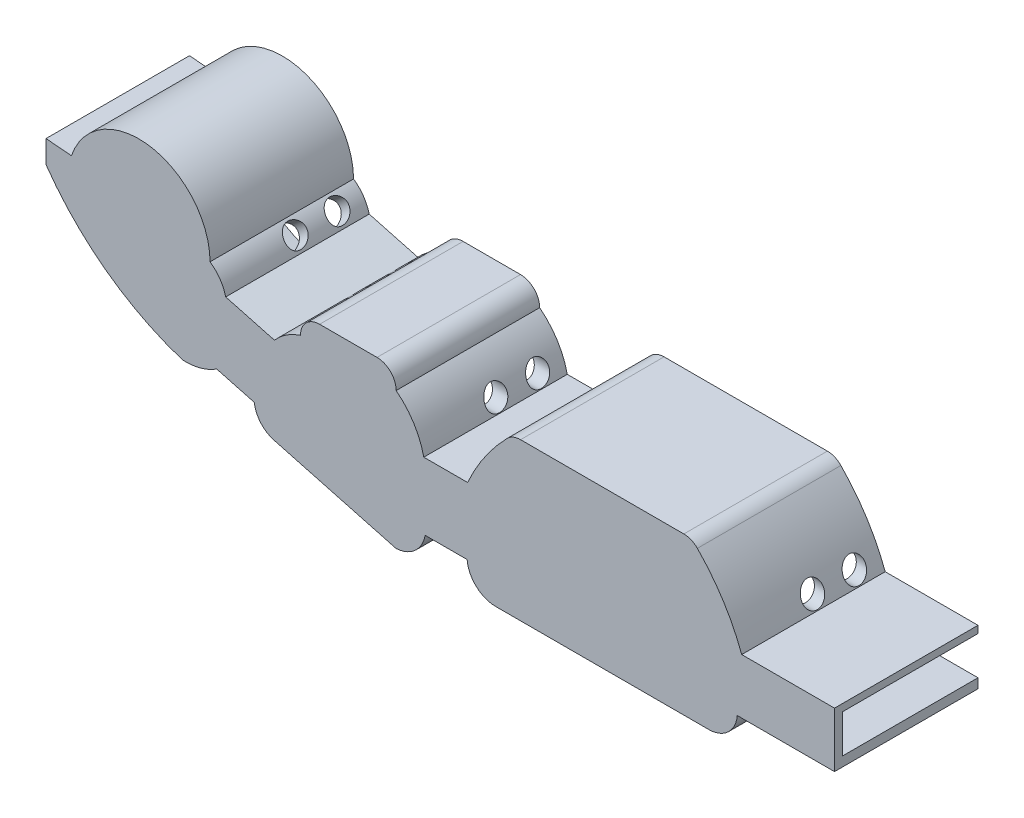
SolidWorks part; units mm, degrees
ref_plane "Front Plane" through (0, 0, 0) normal (0, 0, 1) x (1, 0, 0)
ref_plane "Top Plane" through (0, 0, 0) normal (0, 1, 0) x (1, 0, 0)
ref_plane "Right Plane" through (0, 0, 0) normal (1, 0, 0) x (0, 0, -1)
sketch "Sketch1" plane through (0, 0, 0) normal (0, 0, 1) x (1, 0, 0)
  line L5 (-89.4257, 12.3858) -> (-89.4257, 15.2174)
  line L6 (-89.4257, 15.2174) -> (-86.2372, 14.9459)
  line L11 (-29.6547, 9.152) -> (-29.9579, 10.6577)
  line L13 (-85.3867, 9.2655) -> (-88.6842, 13.2092)
  line L14 (-88.6842, 13.2092) -> (-88.6842, 13.9453)
  line L17 (-88.6842, 13.9453) -> (-88.2985, 13.5047)
  line L19 (-43.5928, 3.095) -> (-35.5928, 3.095)
  line L20 (-35.5971, -2.905) -> (-43.6235, -2.905)
  line L21 (-55.2174, 10.6822) -> (-55.1336, 10.6822)
  line L22 (-59.126, -2.5288) -> (-46.5703, -5.8983)
  line L23 (-11.1807, 10.652) -> (-11.4807, 9.152)
  line L24 (-11.4807, 9.152) -> (-11.7807, 10.652)
  line L25 (-11.7807, 10.652) -> (-12.4807, 10.652)
  line L30 (-86.6408, 12.3858) -> (-88.2985, 13.5047)
  line L36 (-12.4807, 10.652) -> (-12.7807, 9.152)
  line L40 (-12.7807, 9.152) -> (-13.0807, 10.652)
  line L41 (-13.0807, 10.652) -> (-13.7547, 10.652)
  line L43 (-47.904, 12.2025) -> (-55.104, 12.2025)
  line L44 (-60.579, -3.3191) -> (-45.5122, -7.3625)
  line L47 (-13.7547, 10.652) -> (-14.0547, 9.152)
  line L48 (-14.0547, 9.152) -> (-14.3547, 10.652)
  line L49 (-14.3547, 10.652) -> (-15.0547, 10.652)
  line L50 (-15.0547, 10.652) -> (-15.3547, 9.152)
  line L51 (-15.3547, 9.152) -> (-15.6547, 10.652)
  line L52 (-15.6547, 10.652) -> (-16.3547, 10.652)
  line L53 (-16.3547, 10.652) -> (-16.6547, 9.152)
  line L54 (-16.6547, 9.152) -> (-16.9547, 10.652)
  line L55 (-16.9547, 10.652) -> (-17.6547, 10.652)
  line L56 (-17.6547, 10.652) -> (-17.9547, 9.152)
  line L57 (-17.9547, 9.152) -> (-18.2547, 10.652)
  line L58 (-18.2547, 10.652) -> (-18.9547, 10.652)
  line L59 (-18.9547, 10.652) -> (-19.2547, 9.152)
  line L60 (-19.2547, 9.152) -> (-19.5547, 10.652)
  line L61 (-19.5547, 10.652) -> (-20.2547, 10.652)
  line L62 (-20.2547, 10.652) -> (-20.5547, 9.152)
  line L63 (-20.5547, 9.152) -> (-20.8547, 10.652)
  line L64 (-20.8547, 10.652) -> (-21.5547, 10.652)
  line L65 (-21.5547, 10.652) -> (-21.8547, 9.152)
  line L66 (-21.8547, 9.152) -> (-22.1547, 10.652)
  line L67 (-22.1547, 10.652) -> (-22.8547, 10.652)
  line L68 (-22.8547, 10.652) -> (-23.1547, 9.152)
  line L69 (-23.1547, 9.152) -> (-23.4547, 10.652)
  line L70 (-23.4547, 10.652) -> (-24.1547, 10.652)
  line L71 (-24.1547, 10.652) -> (-24.4547, 9.152)
  line L72 (-24.4547, 9.152) -> (-24.7547, 10.652)
  line L73 (-24.7547, 10.652) -> (-25.4547, 10.652)
  line L74 (-25.4547, 10.652) -> (-25.7547, 9.152)
  line L75 (-25.7547, 9.152) -> (-26.0547, 10.652)
  line L76 (-26.0547, 10.652) -> (-26.7547, 10.652)
  line L77 (-26.7547, 10.652) -> (-27.0547, 9.152)
  line L78 (-27.0547, 9.152) -> (-27.3547, 10.652)
  line L79 (-27.3547, 10.652) -> (-28.0547, 10.652)
  line L80 (-28.0547, 10.652) -> (-28.3547, 9.152)
  line L81 (-28.3547, 9.152) -> (-28.6547, 10.652)
  line L82 (-28.6547, 10.652) -> (-29.3547, 10.652)
  line L83 (-29.3547, 10.652) -> (-29.6547, 9.152)
  line L100 (-49.2174, 10.6822) -> (-49.3596, 10.6822)
  line L101 (-49.3596, 10.6822) -> (-49.6596, 9.1822)
  line L102 (-49.6596, 9.1822) -> (-49.9596, 10.6822)
  line L103 (-49.9596, 10.6822) -> (-50.6596, 10.6822)
  line L104 (-50.6596, 10.6822) -> (-50.9596, 9.1822)
  line L105 (-50.9596, 9.1822) -> (-51.2596, 10.6822)
  line L106 (-51.2596, 10.6822) -> (-51.9336, 10.6822)
  line L107 (-51.9336, 10.6822) -> (-52.2336, 9.1822)
  line L108 (-52.2336, 9.1822) -> (-52.5336, 10.6822)
  line L109 (-52.5336, 10.6822) -> (-53.2336, 10.6822)
  line L110 (-53.2336, 10.6822) -> (-53.5336, 9.1822)
  line L111 (-53.5336, 9.1822) -> (-53.8336, 10.6822)
  line L112 (-53.8336, 10.6822) -> (-54.5336, 10.6822)
  line L113 (-54.5336, 10.6822) -> (-54.8336, 9.1822)
  line L114 (-54.8336, 9.1822) -> (-55.1336, 10.6822)
  line L118 (-70.5436, 14.8576) -> (-70.8436, 12.8576)
  line L119 (-70.8436, 12.8576) -> (-71.1436, 15.955)
  line L120 (-71.8436, 16.8755) -> (-72.1436, 15.6755)
  line L121 (-72.1436, 15.6755) -> (-72.4436, 17.4876)
  line L122 (-73.1436, 18.0603) -> (-73.4436, 16.9603)
  line L123 (-73.4436, 16.9603) -> (-73.7436, 18.4574)
  line L124 (-74.4436, 18.8313) -> (-74.7436, 17.8313)
  line L125 (-74.7436, 17.8313) -> (-75.0436, 19.0854)
  line L126 (-75.7436, 19.313) -> (-76.0436, 18.263)
  line L127 (-76.0436, 18.263) -> (-76.3436, 19.4536)
  line L128 (-77.0436, 19.5578) -> (-77.3436, 18.4578)
  line L129 (-77.3436, 18.4578) -> (-77.6436, 19.5977)
  line L130 (-78.3448, 19.5875) -> (-78.6448, 18.3969)
  line L131 (-78.6448, 18.3969) -> (-78.9448, 19.5298)
  line L132 (-79.6426, 19.4048) -> (-79.9426, 18.1477)
  line L133 (-79.9426, 18.1477) -> (-80.2426, 19.2451)
  line L134 (-80.9421, 18.9938) -> (-81.2421, 17.6938)
  line L135 (-81.2421, 17.6938) -> (-81.5421, 18.7169)
  line L136 (-82.2402, 18.3139) -> (-82.5402, 16.8139)
  line L137 (-82.5402, 16.8139) -> (-82.8402, 17.886)
  line L138 (-83.5418, 17.2662) -> (-83.8418, 15.3662)
  line L139 (-83.8418, 15.3662) -> (-84.1418, 16.5999)
  line L148 (-60.7727, 7.6397) -> (-66.8852, 9.2801)
  line L156 (-65.7127, 0.2682) -> (-68.01, 0.8847)
  line L157 (-65.7127, 0.2682) -> (-63.3052, -0.3779)
  line L161 (-68.1187, 8.3687) -> (-60.3921, 6.2951)
  line L162 (-69.2607, 2.4628) -> (-61.42, 0.3587)
  line L163 (-41.8722, -4.105) -> (-36.6012, -4.105)
  line L164 (-42.0381, 4.295) -> (-36.5408, 4.295)
  line L167 (-19.6577, -6.2141) -> (-19.6577, -1.2141) construction
  line L168 (-32.5691, -6.2141) -> (-6.7463, -6.2141)
  line L169 (-29.8968, 12.2681) -> (-9.4143, 12.2681)
  line L170 (-19.6556, 4.8532) -> (-19.6556, 21.169) construction
  line L171 (8.2817, 1.895) -> (-3.6348, 1.895)
  line L172 (-10.5067, 10.652) -> (-11.1807, 10.652)
  line L173 (-9.9067, 10.652) -> (-9.3532, 10.652)
  line L174 (-6.3025, -7.4141) -> (-33.013, -7.4141)
  line L176 (-9.9067, 10.652) -> (-10.2067, 9.152)
  line L177 (-10.2067, 9.152) -> (-10.5067, 10.652)
  line L178 (-9.3532, 4.8532) -> (-9.3532, 10.652) construction
  line L179 (-3.7183, -2.905) -> (8.2817, -2.905)
  line L180 (-2.7142, -4.105) -> (9.4817, -4.105)
  line L183 (9.4817, 2.795) -> (9.4817, -4.105)
  line L184 (8.2817, 1.895) -> (8.2817, -2.905)
  line L185 (-2.1578, 2.795) -> (9.4817, 2.795)
  arc A2 (-85.3867, 9.2655) -> (-72.763, 0.8179) centre (-64.6402, 26.6123) ccw
  arc A5 (-29.9579, 10.6577) -> (-31.4838, 9.9746) centre (-29.9814, 8.6645) ccw
  arc A6 (-31.9681, 8.6822) -> (-35.5928, 3.095) centre (-27.6976, 1.9424) ccw
  arc A8 (-31.4838, 9.9746) -> (-31.9681, 8.6822) centre (-30.0017, 8.6822) ccw
  arc A14 (-69.8436, 11.2299) -> (-70.5436, 14.8576) centre (-77.8767, 11.5612) ccw
  arc A15 (-71.1436, 15.955) -> (-71.8436, 16.8755) centre (-77.8767, 11.5612) ccw
  arc A16 (-72.4436, 17.4876) -> (-73.1436, 18.0603) centre (-77.8767, 11.5612) ccw
  arc A19 (-35.5971, -2.905) -> (-32.5691, -6.2141) centre (-32.6131, -3.2144) ccw
  arc A25 (-73.7436, 18.4574) -> (-74.4436, 18.8313) centre (-77.8767, 11.5612) ccw
  arc A26 (-46.5703, -5.8983) -> (-43.6235, -2.905) centre (-46.8823, -2.644) ccw
  arc A27 (-61.42, 0.3587) -> (-59.126, -2.5288) centre (-58.5468, 0.2864) ccw
  arc A28 (-68.01, 0.8847) -> (-72.3211, -0.2669) centre (-71.9411, 6.9561) cw
  arc A29 (-75.0436, 19.0854) -> (-75.7436, 19.313) centre (-77.8767, 11.5612) ccw
  arc A30 (-76.3436, 19.4536) -> (-77.0436, 19.5578) centre (-77.8767, 11.5612) ccw
  arc A31 (-36.5408, 4.295) -> (-31.5909, 11.551) centre (-13.9301, -5.8132) cw
  arc A33 (-77.6436, 19.5977) -> (-78.3448, 19.5875) centre (-77.8767, 11.5612) ccw
  arc A34 (-72.763, 0.8179) -> (-69.2607, 2.4628) centre (-71.9865, 3.7157) ccw
  arc A37 (-68.1187, 8.3687) -> (-69.8436, 11.2299) centre (-72.1325, 7.8995) ccw
  arc A38 (-57.2174, 8.6822) -> (-60.3921, 6.2951) centre (-55.3158, 2.8486) ccw
  arc A41 (-43.5928, 3.095) -> (-47.2174, 8.6822) centre (-51.488, 1.9424) ccw
  arc A42 (-47.2174, 8.6822) -> (-49.2174, 10.6822) centre (-49.2174, 8.6822) ccw
  arc A43 (-55.2174, 10.6822) -> (-57.2174, 8.6822) centre (-55.2174, 8.6822) ccw
  arc A45 (-85.8314, 12.7286) -> (-86.6408, 12.3858) centre (-79.3152, -3.7856) ccw
  arc A47 (-29.8968, 12.2681) -> (-31.5909, 11.551) centre (-29.8968, 9.9085) ccw
  arc A48 (-78.9448, 19.5298) -> (-79.6426, 19.4048) centre (-77.8767, 11.5612) ccw
  arc A49 (-36.6012, -4.105) -> (-33.013, -7.4141) centre (-33.013, -3.8141) ccw
  arc A51 (-80.2426, 19.2451) -> (-80.9421, 18.9938) centre (-77.8767, 11.5612) ccw
  arc A52 (-81.5421, 18.7169) -> (-82.2402, 18.3139) centre (-77.8767, 11.5612) ccw
  arc A55 (-45.5122, -7.3625) -> (-41.8722, -4.105) centre (-45.7396, -3.446) ccw
  arc A56 (-63.3052, -0.3779) -> (-60.579, -3.3191) centre (-59.884, 0.0591) ccw
  arc A57 (-82.8402, 17.886) -> (-83.5418, 17.2662) centre (-77.8767, 11.5612) ccw
  arc A58 (-89.4257, 12.3858) -> (-72.3211, -0.2669) centre (-62.0173, 31.5502) ccw
  arc A59 (-66.8852, 9.2801) -> (-68.8466, 12.1147) centre (-71.5933, 8.1183) ccw
  arc A60 (-57.504, 9.8025) -> (-60.7727, 7.6397) centre (-55.222, 2.8022) ccw
  arc A61 (-42.0381, 4.295) -> (-45.504, 9.8025) centre (-51.3924, 2.2526) ccw
  arc A62 (-45.504, 9.8025) -> (-47.904, 12.2025) centre (-47.904, 9.8025) ccw
  arc A63 (-55.104, 12.2025) -> (-57.504, 9.8025) centre (-55.104, 9.8025) ccw
  arc A64 (-86.2372, 14.9459) -> (-68.8466, 12.1147) centre (-77.7779, 12.081) cw
  arc A65 (-84.1418, 16.5999) -> (-85.8314, 12.7286) centre (-77.8767, 11.5612) ccw
  arc A66 (-2.7142, -4.105) -> (-6.3025, -7.4141) centre (-6.3025, -3.8141) cw
  arc A67 (-3.7183, -2.905) -> (-6.7463, -6.2141) centre (-6.7023, -3.2144) cw
  arc A69 (-7.343, 8.6822) -> (-9.3532, 10.652) centre (-10.3911, 7.5822) ccw
  arc A70 (-7.343, 8.6822) -> (-3.6348, 1.895) centre (-11.6135, 1.9424) cw
  arc A71 (-2.1578, 2.795) -> (-7.7202, 11.551) centre (-25.381, -5.8132) ccw
  arc A72 (-9.4143, 12.2681) -> (-7.7202, 11.551) centre (-9.4143, 9.9085) cw
  point P92 (-21.3666, 12.2681)
  dimension "D1" = 6
  dimension "D26" = 4.0411
  dimension "D27" = 4.8493
  dimension "D28" = 8.9313
  dimension "D29" = 8.0399
  dimension "D23" = 3.3409
  dimension "D4" = 6
  dimension "D2" = 1.2
  dimension "D3" = 1.2
  dimension "D5" = 1.2
  dimension "D6" = 1.2
  dimension "D7" = 43.8788
  dimension "D8" = 8
  dimension "D9" = 8
  dimension "D10" = 18.0933
  dimension "D11" = 20.0133
  dimension "D12" = 5.271
  dimension "D13" = 3.6247
  dimension "D14" = 12
  dimension "D15" = 5
  dimension "D16" = 5.6348
  dimension "D17" = 5.4973
  dimension "D18" = 4.8
  dimension "D19" = 6.9
  dimension "D20" = 11.9164
  dimension "D21" = 8.0264
  dimension "D22" = 8.1181
  dimension "D24" = 94.113
  dimension "D25" = 6.3288
  dimension "D30" = 3.4471
  dimension "D31" = 5.0053
extrude "Walls" add sketch "Sketch1" along normal blind 16 contours A59 A64 L6 L5 A58 A28 A56 L44 A55 A49 L169 A47 A31 A61 A62 L43 A63 A60 A45 A37 A38 A43 A42 A41 L19 A6 region at (-88.3966, 13.8016, 0)
sketch "Sketch2" plane through (0, 0, 0) normal (0, 0, -1) x (-1, 0, 0)
  line L10 (66.8852, 9.2801) -> (60.7727, 7.6397)
  line L11 (66.8852, 9.2801) -> (60.7727, 7.6397)
  line L12 (63.3052, -0.3779) -> (68.01, 0.8847)
  line L13 (63.3052, -0.3779) -> (68.01, 0.8847)
  line L14 (55.104, 12.2025) -> (47.904, 12.2025)
  line L15 (2.1578, 2.795) -> (-9.4817, 2.795)
  line L16 (29.8968, 12.2681) -> (9.4143, 12.2681)
  line L17 (2.1578, 2.795) -> (-9.4817, 2.795)
  line L18 (-9.4817, 2.795) -> (-9.4817, -4.105)
  line L19 (45.5122, -7.3625) -> (60.579, -3.3191)
  line L22 (89.4257, 12.3858) -> (89.4257, 15.2174)
  line L26 (55.104, 12.2025) -> (47.904, 12.2025)
  line L28 (29.8968, 12.2681) -> (9.4143, 12.2681)
  line L31 (45.5122, -7.3625) -> (60.579, -3.3191)
  line L37 (-9.4817, 2.795) -> (-9.4817, -4.105)
  line L38 (-9.4817, -4.105) -> (2.7142, -4.105)
  line L39 (-9.4817, -4.105) -> (2.7142, -4.105)
  line L40 (6.3025, -7.4141) -> (33.013, -7.4141)
  line L41 (6.3025, -7.4141) -> (33.013, -7.4141)
  line L42 (36.6012, -4.105) -> (41.8722, -4.105)
  line L43 (36.6012, -4.105) -> (41.8722, -4.105)
  line L44 (42.0381, 4.295) -> (36.5408, 4.295)
  line L45 (42.0381, 4.295) -> (36.5408, 4.295)
  line L46 (89.4257, 12.3858) -> (89.4257, 15.2174)
  line L47 (89.4257, 15.2174) -> (86.2372, 14.9459)
  line L48 (89.4257, 15.2174) -> (86.2372, 14.9459)
  arc A16 (9.4143, 12.2681) -> (7.7202, 11.551) centre (9.4143, 9.9085) ccw
  arc A17 (9.4143, 12.2681) -> (7.7202, 11.551) centre (9.4143, 9.9085) ccw
  arc A18 (68.8466, 12.1147) -> (66.8852, 9.2801) centre (71.5933, 8.1183) ccw
  arc A19 (60.7727, 7.6397) -> (57.504, 9.8025) centre (55.222, 2.8022) ccw
  arc A20 (57.504, 9.8025) -> (55.104, 12.2025) centre (55.104, 9.8025) ccw
  arc A21 (47.904, 12.2025) -> (45.504, 9.8025) centre (47.904, 9.8025) ccw
  arc A22 (45.504, 9.8025) -> (42.0381, 4.295) centre (51.3924, 2.2526) ccw
  arc A23 (36.5408, 4.295) -> (31.5909, 11.551) centre (13.9301, -5.8132) ccw
  arc A24 (31.5909, 11.551) -> (29.8968, 12.2681) centre (29.8968, 9.9085) ccw
  arc A25 (7.7202, 11.551) -> (2.1578, 2.795) centre (25.381, -5.8132) ccw
  arc A26 (7.7202, 11.551) -> (2.1578, 2.795) centre (25.381, -5.8132) ccw
  arc A27 (2.7142, -4.105) -> (6.3025, -7.4141) centre (6.3025, -3.8141) ccw
  arc A28 (2.7142, -4.105) -> (6.3025, -7.4141) centre (6.3025, -3.8141) ccw
  arc A30 (33.013, -7.4141) -> (36.6012, -4.105) centre (33.013, -3.8141) ccw
  arc A31 (41.8722, -4.105) -> (45.5122, -7.3625) centre (45.7396, -3.446) ccw
  arc A32 (60.579, -3.3191) -> (63.3052, -0.3779) centre (59.884, 0.0591) ccw
  arc A33 (68.01, 0.8847) -> (72.3211, -0.2669) centre (71.9411, 6.9561) ccw
  arc A34 (72.3211, -0.2669) -> (89.4257, 12.3858) centre (62.0173, 31.5502) ccw
  arc A35 (86.2372, 14.9459) -> (68.8466, 12.1147) centre (77.7779, 12.081) ccw
  arc A36 (68.8466, 12.1147) -> (66.8852, 9.2801) centre (71.5933, 8.1183) ccw
  arc A37 (60.7727, 7.6397) -> (57.504, 9.8025) centre (55.222, 2.8022) ccw
  arc A38 (57.504, 9.8025) -> (55.104, 12.2025) centre (55.104, 9.8025) ccw
  arc A39 (47.904, 12.2025) -> (45.504, 9.8025) centre (47.904, 9.8025) ccw
  arc A40 (45.504, 9.8025) -> (42.0381, 4.295) centre (51.3924, 2.2526) ccw
  arc A41 (36.5408, 4.295) -> (31.5909, 11.551) centre (13.9301, -5.8132) ccw
  arc A42 (31.5909, 11.551) -> (29.8968, 12.2681) centre (29.8968, 9.9085) ccw
  arc A48 (33.013, -7.4141) -> (36.6012, -4.105) centre (33.013, -3.8141) ccw
  arc A49 (41.8722, -4.105) -> (45.5122, -7.3625) centre (45.7396, -3.446) ccw
  arc A50 (60.579, -3.3191) -> (63.3052, -0.3779) centre (59.884, 0.0591) ccw
  arc A51 (68.01, 0.8847) -> (72.3211, -0.2669) centre (71.9411, 6.9561) ccw
  arc A52 (72.3211, -0.2669) -> (89.4257, 12.3858) centre (62.0173, 31.5502) ccw
  arc A53 (86.2372, 14.9459) -> (68.8466, 12.1147) centre (77.7779, 12.081) ccw
  dimension "D1" = 0
extrude "Base" add sketch "Sketch2" along normal blind 1
sketch "Sketch3" [suppressed] plane through (0, 0, 0) normal (0, 0, 1) x (1, 0, 0)
  line L4 (-65.1711, 5.3832) -> (-63.3958, 4.9067) construction
  line L5 (-84.8697, 19.5134) -> (-85.1843, 17.3997) construction
  line L6 (-51.77, 3.095) -> (-68.5693, 3.095) construction
  line L7 (-68.5693, 6.2951) -> (-68.5693, 3.095) construction
  line L8 (-51.77, 3.095) -> (-54.6697, 3.095) construction
  line L9 (-68.5693, 6.2951) -> (-65.1711, 5.3832) construction
  line L10 (-56.4697, 3.095) -> (-54.6697, 3.095) construction
  line L11 (-80.595, 9.5224) -> (-82.2789, 9.9743)
  line L12 (-80.595, 9.5224) -> (-76.2959, 8.3687) construction
  line L13 (-91.8537, 12.2226) -> (-90.116, 11.8146)
  line L14 (-82.2789, 9.9743) -> (-90.116, 11.8146) construction
  line L15 (-40.77, 3.095) -> (-37.27, 3.095) construction
  line L16 (-3.6422, 1.595) -> (-7.1422, 1.595) construction
  line L17 (-40.77, 3.095) -> (-3.7183, 3.095) construction
  line L18 (-22.2442, 8.652) -> (-22.2442, 3.095) construction
  line L19 (-22.8547, 10.652) -> (-22.1547, 10.652) construction
  line L20 (-22.2442, 10.652) -> (-22.2442, 8.652) construction
  line L21 (-37.27, 3.095) -> (-34.1769, 3.095) construction
  line L22 (-11.7175, 3.095) -> (-7.1422, 1.595) construction
  arc A1 (-82.2789, 9.9743) -> (-90.116, 11.8146) centre (-86.0365, 11.58) ccw
  arc A2 (-91.8537, 12.2226) -> (-80.595, 9.5224) centre (-86.0443, 11.6231) cw
  arc A3 (-54.6697, 3.095) -> (-65.1711, 5.3832) centre (-60.1697, 3.095) ccw construction
  arc A4 (-84.5208, 19.4536) -> (-85.2208, 19.5578) centre (-86.0539, 11.5612) ccw construction
  arc A5 (-56.4697, 3.095) -> (-63.3958, 4.9067) centre (-60.1697, 3.095) ccw construction
  arc A6 (-3.6422, 1.595) -> (-7.343, 8.6822) centre (-11.6135, 1.9424) ccw construction
  arc A7 (-7.1422, 1.595) -> (-37.27, 3.095) centre (-22.9472, -12.5401) ccw construction
  arc A8 (-11.7175, 3.095) -> (-34.1769, 3.095) centre (-22.9472, -12.5401) ccw construction
  dimension "D1" = 11
  dimension "D2" = 2.137
  dimension "D3" = 7.4
  dimension "D8" = 38.5
  dimension "D4" = 3.5184
  dimension "D5" = 3.5
  dimension "D6" = 3.5
  dimension "D7" = 2
sketch "Sketch4" [suppressed] plane through (0, 0, 16) normal (0, 0, 1) x (1, 0, 0)
  line L7 (-69.5947, 0.3005) -> (-71.4824, -0.3779)
  line L10 (-71.4824, -0.3779) -> (-76.1872, 0.8847)
  line L11 (-76.1872, 0.8847) -> (-77.6773, 2.0433)
  line L12 (-40.77, 3.095) -> (-41.1043, 4.1128)
  line L13 (-41.1043, 4.1128) -> (-49.5364, 4.1128)
  line L16 (-67.7226, 6.3478) -> (-68.9499, 7.6397)
  line L17 (-68.9499, 7.6397) -> (-75.0624, 9.2801)
  line L18 (-75.0624, 9.2801) -> (-76.3177, 7.7352)
  line L19 (-49.5364, 4.1128) -> (-51.77, 3.095)
  line L20 (-40.7743, -2.905) -> (-41.0926, -4.1129)
  line L21 (-41.0926, -4.1129) -> (-49.3636, -4.1129)
  line L22 (-49.3636, -4.1129) -> (-51.8007, -2.905)
  arc A0 (-67.7226, 6.3478) -> (-76.3177, 7.7352) centre (-69.7742, 20.955) cw
  arc A1 (-69.5947, 0.3005) -> (-77.6773, 2.0433) centre (-76.3689, -11.5028) ccw
  arc A2 (-40.7743, -2.905) -> (-51.8007, -2.905) centre (-46.2875, -28.5004) ccw
  arc A3 (-40.77, 3.095) -> (-51.77, 3.095) centre (-46.27, 28.5687) cw
extrude "Joint Width" [suppressed] add sketch "Sketch4" against normal blind 16
ref_plane "SideAnchorPlane" through (0, 0, 2.5) normal (0, 0, 1) x (1, 0, 0)
ref_plane "CentralAnchorPlane" through (0, 0, 13) normal (0, 0, 1) x (1, 0, 0)
sketch "Sketch5" [suppressed] plane through (0, 0, 3) normal (0, 0, 1) x (1, 0, 0)
  line L0 (-76.2959, 8.3687) -> (-68.5693, 6.2951) construction
  line L1 (-76.592, 9.4835) -> (-67.8744, 7.144) construction
  line L2 (-77.4258, 10.7304) -> (-66.9487, 7.9187) construction
  line L3 (-76.592, 9.4835) -> (-88.7757, 4.7797)
  line L4 (-77.4258, 10.7304) -> (-90.1205, 5.8293)
  line L5 (-78.0158, 11.7317) -> (-91.096, 6.6818)
  line L6 (-76.2959, 8.3687) -> (-87.6359, 3.9906)
  line L7 (-78.0158, 11.7317) -> (-77.4258, 10.7304)
  line L9 (-76.592, 9.4835) -> (-76.0479, 8.9395)
  line L10 (-76.0479, 8.9395) -> (-76.2959, 8.3687)
  line L11 (-91.096, 6.6818) -> (-91.096, 6.0024)
  line L12 (-91.096, 6.0024) -> (-90.1205, 5.8293)
  line L13 (-88.7757, 4.7797) -> (-88.5883, 3.9906)
  line L14 (-88.5883, 3.9906) -> (-87.6359, 3.9906)
  arc A0 (-76.2959, 8.3687) -> (-78.0208, 11.2299) centre (-80.3097, 7.8995) ccw construction
  arc A1 (-65.3947, 8.6822) -> (-68.5693, 6.2951) centre (-63.493, 2.8486) ccw construction
  arc A2 (-76.2959, 8.3687) -> (-78.0208, 11.2299) centre (-80.3097, 7.8995) ccw construction
  arc A4 (-93.5639, 9.2655) -> (-80.9402, 0.8179) centre (-72.8174, 26.6123) ccw construction
  arc A5 (-93.5639, 9.2655) -> (-80.9402, 0.8179) centre (-72.8174, 26.6123) ccw construction
  dimension "D1" = 1
  dimension "D2" = 1.5
  dimension "D3" = 1.1466
  dimension "D4" = 1.1466
extrude "Boss-Extrude2" [suppressed] add sketch "Sketch5" along normal blind 1 and the other way blind 1 separate body
sketch "Sketch6" [suppressed] plane through (0, 0, 4) normal (0, 0, 1) x (1, 0, 0)
  line L1 (-87.6359, 3.9906) -> (-76.2959, 8.3687)
  line L4 (-78.0158, 11.7317) -> (-91.096, 6.6818)
  line L5 (-91.096, 6.6818) -> (-91.7792, 6.284)
  line L6 (-91.7792, 6.284) -> (-88.4163, 3.7031)
  line L7 (-88.4163, 3.7031) -> (-87.6359, 3.9906)
  line L8 (-78.0158, 11.7317) -> (-75.9969, 10.8669)
  line L9 (-75.9969, 10.8669) -> (-76.2959, 8.3687)
  arc A0 (-93.5639, 9.2655) -> (-80.9402, 0.8179) centre (-72.8174, 26.6123) ccw construction
extrude "Boss-Extrude4" [suppressed] add sketch "Sketch6" along normal blind 1
sketch "Sketch7" [suppressed] plane through (0, 0, 2) normal (0, 0, -1) x (-1, 0, 0)
  line L0 (87.6359, 3.9906) -> (90.1015, 4.9746)
  line L1 (90.1015, 4.9746) -> (91.096, 6.6818)
  line L2 (91.096, 6.6818) -> (78.0158, 11.7317)
  line L3 (78.0158, 11.7317) -> (76.2959, 10.4542)
  line L4 (76.2959, 10.4542) -> (76.2959, 8.3687)
  line L5 (76.2959, 8.3687) -> (87.6359, 3.9906)
extrude "Boss-Extrude5" [suppressed] add sketch "Sketch7" along normal blind 1
extrude "Boss-Extrude6" [suppressed] add sketch "Sketch3" along normal up to surface (16 mm away)
ref_plane "Plane3" through (-55, 0, 0) normal (1, 0, 0) x (0, 0, -1)
sketch "Sketch14" plane through (-55, 0, 0) normal (1, 0, 0) x (0, 0, -1)
  line L0 (-16, 3.095) -> (1, 3.095) construction
  line L1 (1, 2.795) -> (1, 11.551) construction
  line L2 (-16, 8.4472) -> (1, 8.4472) construction
  line L4 (-7.5, 8.4472) -> (-7.5, 3.095) construction
  line L6 (-7.5, 5.7711) -> (-16, 5.7711) construction
  line L7 (-16, 8.6822) -> (-16, 3.095) construction
  line L8 (-16, 8.4472) -> (-16, 3.095) construction
  circle A4 centre (-12.75, 5.7711) radius 1.4 construction
  circle A5 centre (-2.25, 5.7711) radius 1.4
  circle A6 centre (-7.5, 5.7711) radius 1.4
  dimension "D1" = 2.8
  dimension "D2" = 5.25
extrude "Cut-Extrude2" cut sketch "Sketch14" along normal up to surface (20.3022 mm away) up to face at (-34.0858, 6.0868, 8)
sketch "Sketch15" plane through (0, 0, 0) normal (1, 0, 0) x (0, 0, -1)
  line L1 (-16, 2.795) -> (1, 2.795) construction
  line L5 (1, 2.795) -> (1, 5.795) construction
  line L6 (1, 2.795) -> (1, 11.551) construction
  line L7 (1, 5.795) -> (-16, 5.795) construction
  line L8 (-7.5, 5.795) -> (-7.5, 2.795) construction
  line L9 (-16, 11.551) -> (-16, 2.795) construction
  line L10 (-7.5, 4.295) -> (-16, 4.295) construction
  circle A4 centre (-12.75, 4.295) radius 1.4 construction
  circle A5 centre (-2.25, 4.295) radius 1.4
  circle A6 centre (-7.5, 4.295) radius 1.4
  dimension "D2" = 5.25
  dimension "D1" = 2.8
extrude "Cut-Extrude3" cut sketch "Sketch15" against normal up to surface (3.9894 mm away) up to face at (-5.0502, 5.5283, 8)
ref_plane "Plane4" through (-34.7065, -29.0992, 0) normal (0.7663, 0.6425, 0) x (0, 0, -1)
sketch "Sketch16" plane through (-34.7065, -29.0992, 0) normal (0.7663, 0.6425, 0) x (0, 0, -1)
  line L1 (-2.5, 57.2123) -> (-13, 57.2123) construction
  line L2 (-13, 55) -> (-13, -55) construction
  line L3 (-16, 53.5167) -> (-16, 50.0844) construction
  line L4 (1, 53.5167) -> (1, 50.0844) construction
  line L6 (-16, 51.8005) -> (1, 51.8005) construction
  line L7 (-7.75, 57.2123) -> (-13, 57.2123) construction
  line L10 (-16, 53.5167) -> (1, 53.5167) construction
  line L11 (-16, 50.0844) -> (1, 50.0844) construction
  line L12 (-16, 53.5167) -> (1, 53.5167) construction
  line L13 (-7.5, 53.5167) -> (-7.5, 50.0844) construction
  circle A0 centre (-2.5, 57.2123) radius 1.4 construction
  circle A1 centre (-13, 57.2123) radius 1.4 construction
  circle A2 centre (-12.75, 51.8005) radius 1.4 construction
  circle A3 centre (-2.25, 51.8005) radius 1.4
  circle A4 centre (-7.5, 51.8005) radius 1.4
  dimension "D1" = 2.8
  dimension "D4" = 5.25
  dimension "D5" = 2.8
  dimension "D2" = 17
  dimension "D3" = 5.25
extrude "Cut-Extrude4" cut sketch "Sketch16" against normal up to surface and the other way up to surface up to face at (-81.3899, 5.3613, 7.5) other way up to face at (-67.7357, 10.7875, 7.5)
ref_plane "Plane5" through (-56.1061, 20.4456, 0) normal (-0.9396, 0.3424, 0) x (0, 0, -1)
sketch "Sketch18" plane through (-56.1061, 20.4456, 0) normal (-0.9396, 0.3424, 0) x (0, 0, -1)
  line L0 (-16, 10.4785) -> (1, 10.4785) construction
  line L1 (1, 10.4785) -> (1, 10.7785) construction
  line L2 (1, 10.4785) -> (1, 13.6297) construction
  line L3 (1, 10.7785) -> (-16, 10.7785) construction
  line L4 (-16, 13.6297) -> (-16, 10.4785) construction
  line L5 (-7.5, 10.7785) -> (-7.5, 10.4785) construction
  line L6 (-7.5, 13.3074) -> (-7.5, 10.7785) construction
  circle A2 centre (-12.75, 12.1785) radius 1.4 construction
  circle A3 centre (-2.25, 12.1785) radius 1.4
  circle A4 centre (-7.5, 12.1785) radius 1.4
  dimension "D1" = 2.8
  dimension "D2" = 5.25
  dimension "D3" = 0.3
extrude "Cut-Extrude5" cut sketch "Sketch18" against normal up to surface (1.2501 mm away) up to face at (-58.904, 7.6207, 8)
sketch "Sketch19" plane through (0, 0, 0) normal (0, 0, 1) x (1, 0, 0)
  line L115 (-12.7807, 9.152) -> (-13.0807, 10.652)
  line L116 (-16.6547, 9.152) -> (-16.9547, 10.652)
  line L117 (-22.8547, 10.652) -> (-23.1547, 9.152)
  line L118 (-28.0547, 10.652) -> (-28.3547, 9.152)
  line L122 (-74.4436, 18.8313) -> (-74.7436, 17.8313)
  line L123 (-82.5402, 16.8139) -> (-82.8402, 17.886)
  line L126 (-11.1807, 10.652) -> (-11.4807, 9.152)
  line L472 (-17.9547, 9.152) -> (-18.2547, 10.652)
  line L473 (-27.0547, 9.152) -> (-27.3547, 10.652)
  line L474 (-51.9336, 10.6822) -> (-52.2336, 9.1822)
  line L475 (-79.9426, 18.1477) -> (-80.2426, 19.2451)
  line L476 (-9.9067, 10.652) -> (-9.3532, 10.652)
  line L477 (-19.6577, -6.2141) -> (-19.6577, -1.2141) construction
  line L478 (-88.6842, 13.9453) -> (-88.2985, 13.5047)
  line L479 (-16.3547, 10.652) -> (-16.6547, 9.152)
  line L480 (-24.1547, 10.652) -> (-24.4547, 9.152)
  line L481 (-52.5336, 10.6822) -> (-53.2336, 10.6822)
  line L482 (-81.2421, 17.6938) -> (-81.5421, 18.7169)
  line L483 (-69.2607, 2.4628) -> (-61.42, 0.3587)
  line L484 (-59.126, -2.5288) -> (-46.5703, -5.8983)
  line L485 (-19.2547, 9.152) -> (-19.5547, 10.652)
  line L486 (-26.0547, 10.652) -> (-26.7547, 10.652)
  line L487 (-50.6596, 10.6822) -> (-50.9596, 9.1822)
  line L488 (-72.1436, 15.6755) -> (-72.4436, 17.4876)
  line L489 (-10.2067, 9.152) -> (-10.5067, 10.652)
  line L490 (-9.3532, 4.8532) -> (-9.3532, 10.652) construction
  line L491 (-11.7807, 10.652) -> (-12.4807, 10.652)
  line L492 (-21.8547, 9.152) -> (-22.1547, 10.652)
  line L493 (-52.2336, 9.1822) -> (-52.5336, 10.6822)
  line L494 (-54.8336, 9.1822) -> (-55.1336, 10.6822)
  line L495 (-3.7183, -2.905) -> (8.2817, -2.905)
  line L496 (-43.5928, 3.095) -> (-35.5928, 3.095)
  line L497 (-16.9547, 10.652) -> (-17.6547, 10.652)
  line L498 (-24.4547, 9.152) -> (-24.7547, 10.652)
  line L499 (-28.3547, 9.152) -> (-28.6547, 10.652)
  line L500 (-74.7436, 17.8313) -> (-75.0436, 19.0854)
  line L501 (-32.5691, -6.2141) -> (-6.7463, -6.2141)
  line L502 (-13.0807, 10.652) -> (-13.7547, 10.652)
  line L503 (-18.9547, 10.652) -> (-19.2547, 9.152)
  line L504 (-27.3547, 10.652) -> (-28.0547, 10.652)
  line L505 (-53.2336, 10.6822) -> (-53.5336, 9.1822)
  line L506 (-75.7436, 19.313) -> (-76.0436, 18.263)
  line L507 (-14.3547, 10.652) -> (-15.0547, 10.652)
  line L508 (-15.0547, 10.652) -> (-15.3547, 9.152)
  line L509 (-24.7547, 10.652) -> (-25.4547, 10.652)
  line L510 (-70.8436, 12.8576) -> (-71.1436, 15.955)
  line L511 (-73.4436, 16.9603) -> (-73.7436, 18.4574)
  line L512 (-9.9067, 10.652) -> (-10.2067, 9.152)
  line L513 (-86.6408, 12.3858) -> (-88.2985, 13.5047)
  line L514 (-20.5547, 9.152) -> (-20.8547, 10.652)
  line L515 (-26.7547, 10.652) -> (-27.0547, 9.152)
  line L516 (-50.9596, 9.1822) -> (-51.2596, 10.6822)
  line L517 (-73.1436, 18.0603) -> (-73.4436, 16.9603)
  line L518 (8.2817, 1.895) -> (8.2817, -2.905)
  line L519 (-85.3867, 9.2655) -> (-88.6842, 13.2092)
  line L520 (-19.5547, 10.652) -> (-20.2547, 10.652)
  line L521 (-23.1547, 9.152) -> (-23.4547, 10.652)
  line L522 (-53.5336, 9.1822) -> (-53.8336, 10.6822)
  line L523 (-77.3436, 18.4578) -> (-77.6436, 19.5977)
  line L524 (-83.8418, 15.3662) -> (-84.1418, 16.5999)
  line L525 (-11.4807, 9.152) -> (-11.7807, 10.652)
  line L526 (-18.2547, 10.652) -> (-18.9547, 10.652)
  line L527 (-25.4547, 10.652) -> (-25.7547, 9.152)
  line L528 (-49.3596, 10.6822) -> (-49.6596, 9.1822)
  line L529 (-76.0436, 18.263) -> (-76.3436, 19.4536)
  line L530 (-82.2402, 18.3139) -> (-82.5402, 16.8139)
  line L531 (-55.2174, 10.6822) -> (-55.1336, 10.6822)
  line L532 (-20.2547, 10.652) -> (-20.5547, 9.152)
  line L533 (-29.3547, 10.652) -> (-29.6547, 9.152)
  line L534 (-53.8336, 10.6822) -> (-54.5336, 10.6822)
  line L535 (-78.3448, 19.5875) -> (-78.6448, 18.3969)
  line L536 (-12.4807, 10.652) -> (-12.7807, 9.152)
  line L537 (-15.3547, 9.152) -> (-15.6547, 10.652)
  line L538 (-22.1547, 10.652) -> (-22.8547, 10.652)
  line L539 (-28.6547, 10.652) -> (-29.3547, 10.652)
  line L540 (-71.8436, 16.8755) -> (-72.1436, 15.6755)
  line L541 (-83.5418, 17.2662) -> (-83.8418, 15.3662)
  line L542 (-19.6556, 4.8532) -> (-19.6556, 21.169) construction
  line L543 (-35.5971, -2.905) -> (-43.6235, -2.905)
  line L544 (-15.6547, 10.652) -> (-16.3547, 10.652)
  line L545 (-49.6596, 9.1822) -> (-49.9596, 10.6822)
  line L546 (-51.2596, 10.6822) -> (-51.9336, 10.6822)
  line L547 (-78.6448, 18.3969) -> (-78.9448, 19.5298)
  line L548 (-10.5067, 10.652) -> (-11.1807, 10.652)
  line L549 (-88.6842, 13.2092) -> (-88.6842, 13.9453)
  line L550 (-20.8547, 10.652) -> (-21.5547, 10.652)
  line L551 (-23.4547, 10.652) -> (-24.1547, 10.652)
  line L552 (-54.5336, 10.6822) -> (-54.8336, 9.1822)
  line L553 (-79.6426, 19.4048) -> (-79.9426, 18.1477)
  line L554 (-68.1187, 8.3687) -> (-60.3921, 6.2951)
  line L555 (-14.0547, 9.152) -> (-14.3547, 10.652)
  line L556 (-17.6547, 10.652) -> (-17.9547, 9.152)
  line L557 (-25.7547, 9.152) -> (-26.0547, 10.652)
  line L558 (-49.9596, 10.6822) -> (-50.6596, 10.6822)
  line L559 (-77.0436, 19.5578) -> (-77.3436, 18.4578)
  line L560 (8.2817, 1.895) -> (-3.6348, 1.895)
  line L561 (-29.6547, 9.152) -> (-29.9579, 10.6577)
  line L562 (-13.7547, 10.652) -> (-14.0547, 9.152)
  line L563 (-21.5547, 10.652) -> (-21.8547, 9.152)
  line L564 (-49.2174, 10.6822) -> (-49.3596, 10.6822)
  line L565 (-70.5436, 14.8576) -> (-70.8436, 12.8576)
  line L566 (-80.9421, 18.9938) -> (-81.2421, 17.6938)
  arc A176 (-29.9579, 10.6577) -> (-31.4838, 9.9746) centre (-29.9814, 8.6645) ccw
  arc A177 (-82.8402, 17.886) -> (-83.5418, 17.2662) centre (-77.8767, 11.5612) ccw
  arc A178 (-85.3867, 9.2655) -> (-72.763, 0.8179) centre (-64.6402, 26.6123) ccw
  arc A179 (-80.2426, 19.2451) -> (-80.9421, 18.9938) centre (-77.8767, 11.5612) ccw
  arc A180 (-55.2174, 10.6822) -> (-57.2174, 8.6822) centre (-55.2174, 8.6822) ccw
  arc A181 (-71.1436, 15.955) -> (-71.8436, 16.8755) centre (-77.8767, 11.5612) ccw
  arc A182 (-72.763, 0.8179) -> (-69.2607, 2.4628) centre (-71.9865, 3.7157) ccw
  arc A183 (-61.42, 0.3587) -> (-59.126, -2.5288) centre (-58.5468, 0.2864) ccw
  arc A184 (-84.1418, 16.5999) -> (-85.8314, 12.7286) centre (-77.8767, 11.5612) ccw
  arc A185 (-31.9681, 8.6822) -> (-35.5928, 3.095) centre (-27.6976, 1.9424) ccw
  arc A186 (-43.5928, 3.095) -> (-47.2174, 8.6822) centre (-51.488, 1.9424) ccw
  arc A187 (-35.5971, -2.905) -> (-32.5691, -6.2141) centre (-32.6131, -3.2144) ccw
  arc A188 (-68.1187, 8.3687) -> (-69.8436, 11.2299) centre (-72.1325, 7.8995) ccw
  arc A189 (-3.7183, -2.905) -> (-6.7463, -6.2141) centre (-6.7023, -3.2144) cw
  arc A190 (-72.4436, 17.4876) -> (-73.1436, 18.0603) centre (-77.8767, 11.5612) ccw
  arc A191 (-85.8314, 12.7286) -> (-86.6408, 12.3858) centre (-79.3152, -3.7856) ccw
  arc A192 (-78.9448, 19.5298) -> (-79.6426, 19.4048) centre (-77.8767, 11.5612) ccw
  arc A193 (-7.343, 8.6822) -> (-9.3532, 10.652) centre (-10.3911, 7.5822) ccw
  arc A194 (-31.4838, 9.9746) -> (-31.9681, 8.6822) centre (-30.0017, 8.6822) ccw
  arc A195 (-76.3436, 19.4536) -> (-77.0436, 19.5578) centre (-77.8767, 11.5612) ccw
  arc A196 (-46.5703, -5.8983) -> (-43.6235, -2.905) centre (-46.8823, -2.644) ccw
  arc A197 (-81.5421, 18.7169) -> (-82.2402, 18.3139) centre (-77.8767, 11.5612) ccw
  arc A198 (-47.2174, 8.6822) -> (-49.2174, 10.6822) centre (-49.2174, 8.6822) ccw
  arc A199 (-73.7436, 18.4574) -> (-74.4436, 18.8313) centre (-77.8767, 11.5612) ccw
  arc A200 (-57.2174, 8.6822) -> (-60.3921, 6.2951) centre (-55.3158, 2.8486) ccw
  arc A201 (-77.6436, 19.5977) -> (-78.3448, 19.5875) centre (-77.8767, 11.5612) ccw
  arc A202 (-7.343, 8.6822) -> (-3.6348, 1.895) centre (-11.6135, 1.9424) cw
  arc A203 (-69.8436, 11.2299) -> (-70.5436, 14.8576) centre (-77.8767, 11.5612) ccw
  arc A204 (-75.0436, 19.0854) -> (-75.7436, 19.313) centre (-77.8767, 11.5612) ccw
  point P261 (-21.3666, 12.2681)
  dimension "D40" = 5.0053
  dimension "D35" = 4.0411
  dimension "D36" = 8.0399
  dimension "D1" = 6
  dimension "D5" = 6
  dimension "D8" = 8
  dimension "D9" = 8
  dimension "D10" = 18.0933
  dimension "D11" = 20.0133
  dimension "D12" = 3.6247
  dimension "D13" = 5
  dimension "D14" = 5.6348
  dimension "D15" = 4.8
  dimension "D16" = 12
  dimension "D17" = 11.9164
  dimension "D18" = 8.0264
  dimension "D19" = 8.1181
  dimension "D20" = 43.8788
  dimension "D29" = 94.113
  dimension "D38" = 3.3409
extrude "Cut-Extrude6" cut sketch "Sketch19" against normal up to surface (1 mm away) up to face at (-42.6602, 4.8771, -1)
sketch "Sketch20" plane through (0, 0, 0) normal (0, 0, 1) x (1, 0, 0)
  line L0 (-86.4793, 6.0116) -> (-84.0003, 8.4287)
  line L1 (-83.666, 8.0563) -> (-86.1302, 5.6536)
  line L2 (-84.0003, 8.4287) -> (-83.666, 8.0563)
  line L3 (-86.1302, 5.6536) -> (-86.4793, 6.0116)
  line L4 (-53.3919, -6.2398) -> (-52.3044, -2.1874)
  line L5 (-74.7588, 2.1835) -> (-75.7904, -0.5519)
  line L6 (-51.8215, -2.3169) -> (-52.909, -6.3694)
  line L7 (-52.909, -6.3694) -> (-53.3919, -6.2398)
  line L8 (-51.8215, -2.3169) -> (-52.3044, -2.1874)
  line L9 (-75.7904, -0.5519) -> (-75.3225, -0.7283)
  line L10 (-24.748, -4.1815) -> (-24.248, -4.1815)
  line L11 (-24.748, -4.1815) -> (-24.748, -10.1505)
  line L12 (-24.748, -10.1505) -> (-24.248, -10.1505)
  line L13 (-24.248, -4.1815) -> (-24.248, -10.1505)
  line L14 (-75.3225, -0.7283) -> (-74.2909, 2.0071)
  line L15 (-74.2909, 2.0071) -> (-74.7588, 2.1835)
  line L16 (-46.5703, -5.8983) -> (-59.126, -2.5288) construction
  line L17 (-88.6842, 13.2092) -> (-72.763, 0.8179) construction
  dimension "D1" = 0.5
  dimension "D2" = 0.5
  dimension "D3" = 0.5
  dimension "D4" = 0.5
extrude "Cut-Extrude7" cut sketch "Sketch20" along normal blind 13 from offset 1
sketch "Sketch21" plane through (0, 0, 0) normal (0, 0, 1) x (1, 0, 0)
  line L0 (9.4817, 2.795) -> (9.4817, -4.105) construction
  line L3 (8.2817, -2.905) -> (9.4817, -2.905)
  line L4 (9.4817, 1.895) -> (9.4817, -2.905)
  line L5 (8.2817, -2.905) -> (8.2817, 1.895)
  line L6 (8.2817, 1.895) -> (9.4817, 1.895)
  dimension "D1" = 4.8
extrude "Cut-Extrude8" cut sketch "Sketch21" against normal up to surface and the other way up to surface up to face at (-45.3091, 10.8418, -1) other way up to face at (-42.6602, 4.8771, 16)
ref_plane "Plane6" through (0, 0, 16) normal (0, 0, 1) x (1, 0, 0)
sketch "Sketch22" plane through (0, 0, 16) normal (0, 0, 1) x (1, 0, 0)
  line L27 (-89.4257, 15.2174) -> (-86.2372, 14.9459)
  line L43 (-47.904, 12.2025) -> (-55.104, 12.2025)
  line L44 (-60.579, -3.3191) -> (-45.5122, -7.3625)
  line L119 (-60.7727, 7.6397) -> (-66.8852, 9.2801)
  line L120 (-65.7127, 0.2682) -> (-68.01, 0.8847)
  line L121 (-65.7127, 0.2682) -> (-63.3052, -0.3779)
  line L124 (-41.8722, -4.105) -> (-36.6012, -4.105)
  line L125 (-42.0381, 4.295) -> (-36.5408, 4.295)
  line L126 (-89.4257, 15.2174) -> (-89.4257, 12.3858)
  line L128 (-29.8968, 12.2681) -> (-9.4143, 12.2681)
  line L133 (-6.3025, -7.4141) -> (-33.013, -7.4141)
  line L138 (-2.7142, -4.105) -> (9.4817, -4.105)
  line L139 (9.4817, 2.795) -> (9.4817, -4.105)
  line L141 (-2.1578, 2.795) -> (9.4817, 2.795)
  arc A43 (-68.01, 0.8847) -> (-72.3211, -0.2669) centre (-71.9411, 6.9561) cw
  arc A46 (-36.5408, 4.295) -> (-31.5909, 11.551) centre (-13.9301, -5.8132) cw
  arc A55 (-29.8968, 12.2681) -> (-31.5909, 11.551) centre (-29.8968, 9.9085) ccw
  arc A57 (-36.6012, -4.105) -> (-33.013, -7.4141) centre (-33.013, -3.8141) ccw
  arc A60 (-45.5122, -7.3625) -> (-41.8722, -4.105) centre (-45.7396, -3.446) ccw
  arc A61 (-63.3052, -0.3779) -> (-60.579, -3.3191) centre (-59.884, 0.0591) ccw
  arc A63 (-89.4257, 12.3858) -> (-72.3211, -0.2669) centre (-62.0173, 31.5502) ccw
  arc A64 (-66.8852, 9.2801) -> (-68.8466, 12.1147) centre (-71.5933, 8.1183) ccw
  arc A65 (-57.504, 9.8025) -> (-60.7727, 7.6397) centre (-55.222, 2.8022) ccw
  arc A66 (-42.0381, 4.295) -> (-45.504, 9.8025) centre (-51.3924, 2.2526) ccw
  arc A67 (-45.504, 9.8025) -> (-47.904, 12.2025) centre (-47.904, 9.8025) ccw
  arc A68 (-55.104, 12.2025) -> (-57.504, 9.8025) centre (-55.104, 9.8025) ccw
  arc A69 (-86.2372, 14.9459) -> (-68.8466, 12.1147) centre (-77.7779, 12.081) cw
  arc A71 (-2.7142, -4.105) -> (-6.3025, -7.4141) centre (-6.3025, -3.8141) cw
  arc A75 (-2.1578, 2.795) -> (-7.7202, 11.551) centre (-25.381, -5.8132) ccw
  arc A76 (-9.4143, 12.2681) -> (-7.7202, 11.551) centre (-9.4143, 9.9085) cw
  point P128 (-21.3666, 12.2681)
  dimension "D26" = 4.8493
  dimension "D27" = 8.9313
  dimension "D15" = 6.9
  dimension "D21" = 5.271
  dimension "D22" = 5.4973
  dimension "D24" = 6.3288
  dimension "D30" = 3.4471
extrude "Boss-Extrude7" add sketch "Sketch22" along normal blind 1
